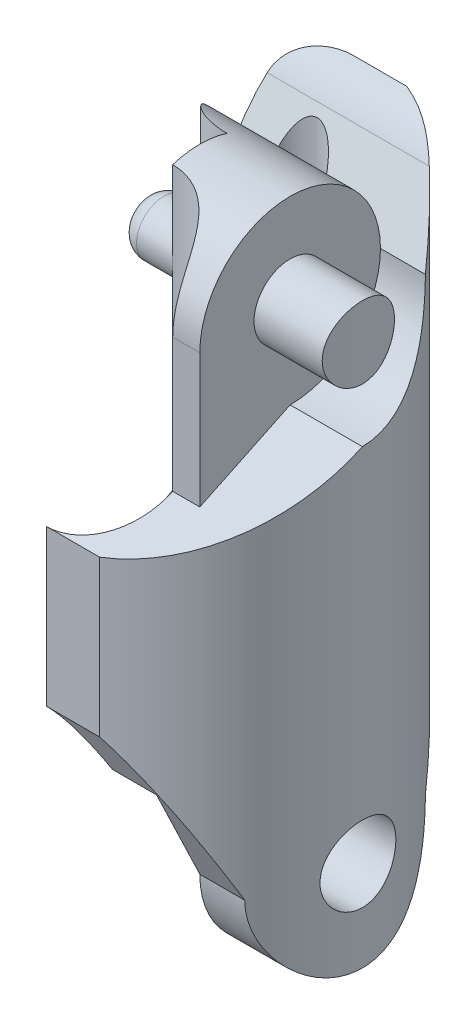
SolidWorks part; units mm, degrees
ref_plane "Front Plane" through (0, 0, 0) normal (0, 0, 1) x (1, 0, 0)
ref_plane "Top Plane" through (0, 0, 0) normal (0, 1, 0) x (1, 0, 0)
ref_plane "Right Plane" through (0, 0, 0) normal (1, 0, 0) x (0, 0, -1)
sketch "Sketch1" plane through (0, 0, 0) normal (0, 1, 0) x (1, 0, 0)
  line L0 (-2.958, 8.5) -> (2.958, 8.5)
  line L1 (-2.958, -8.5) -> (2.958, -8.5)
  arc A0 (-2.958, 8.5) -> (-2.958, -8.5) centre (0, 0) ccw
  arc A1 (2.958, 8.5) -> (2.958, -8.5) centre (0, 0) cw
  point P9 (-9, 0)
  point P10 (9, 0)
  dimension "D1" = 18
  dimension "D2" = 17
extrude "Boss-Extrude1" add sketch "Sketch1" along normal blind 35
sketch "Sketch2" plane through (0, 0, 0) normal (0, -1, 0) x (1, 0, 0)
  line L0 (1.5, -5) -> (-1.5, -5)
  line L1 (1.5, 5) -> (-1.5, 5)
  line L2 (0, 5) -> (0, -5) construction
  arc A0 (-1.5, -5) -> (1.5, -5) centre (0, -5) ccw
  arc A1 (1.5, 5) -> (-1.5, 5) centre (0, 5) ccw
  dimension "D1" = 10
  dimension "D2" = 1.5
extrude "Cut-Extrude1" cut sketch "Sketch2" against normal blind 35
sketch "Sketch3" plane through (0, 0, -8.5) normal (0, 0, -1) x (-1, 0, 0)
  line L0 (5, 0) -> (5, 10)
  line L1 (5, 10) -> (-5, 10)
  line L2 (-5, 10) -> (-5, 0)
  line L3 (5, 0) -> (-5, 0)
  line L4 (-2.958, 0) -> (2.958, 0) construction
  point P10 (0, 0)
  dimension "D1" = 10
  dimension "D2" = 10
extrude "Cut-Extrude2" cut sketch "Sketch3" against normal up to surface (17 mm away) up to face at (0, 17.5, 8.5)
sketch "Sketch4" plane through (5, 0, 0) normal (-1, 0, 0) x (0, 0, 1)
  line L0 (-7.4833, 10) -> (-5, 5)
  line L1 (8.5, 12.3086) -> (5, 5)
  line L2 (7.4833, 0) -> (-7.4833, 0) construction
  line L3 (-7.4833, 10) -> (-9.8579, -1.8222)
  line L4 (-9.8579, -1.8222) -> (9.8579, -1.8222)
  line L6 (8.5, 35) -> (8.5, 10) construction
  line L7 (9.8579, -1.8222) -> (8.5, 12.3086)
  arc A0 (-5, 5) -> (5, 5) centre (0, 5) ccw
  circle A1 centre (0, 5) radius 2.1
  point P7 (0, 0)
  dimension "D1" = 4.2
  dimension "D2" = 5
  dimension "D3" = 12.0584
  dimension "D4" = 37.769
extrude "Cut-Extrude3" cut sketch "Sketch4" against normal mid plane 35
ref_plane "Plane1" through (-2.958, 0, 0) normal (-1, 0, 0) x (0, 0, 1)
sketch "Sketch6" plane through (-2.958, 0, 0) normal (-1, 0, 0) x (0, 0, 1)
  line L0 (8.5, 20.9294) -> (0, 25)
  line L1 (8.5, 35) -> (8.5, 12.3086) construction
  line L2 (-5, 30) -> (-6.7559, 33.5353)
  line L3 (8.5, 35) -> (-8.5, 35) construction
  line L4 (8.5, 20.9294) -> (17.803, 42.886)
  line L6 (-7.4833, 10) -> (-5, 5) construction
  line L7 (-8.5, 35) -> (17.803, 42.886)
  line L8 (5, 5) -> (8.5, 12.3086) construction
  arc A0 (0, 25) -> (-5, 30) centre (0, 30) cw
  circle A1 centre (0, 30) radius 2
  arc A2 (-6.7559, 33.5353) -> (-8.5, 35) centre (-9.3069, 32.2683) ccw
  dimension "D1" = 5
  dimension "D3" = 4
  dimension "D2" = 5
  dimension "D4" = 8.5
  dimension "D5" = 90
extrude "Cut-Extrude5" cut sketch "Sketch6" against normal blind 9.6 from surface starting at face at (5, 7.1, 0)
sketch "Sketch7" plane through (5, 0, 0) normal (1, 0, 0) x (0, 0, -1)
  line L0 (5, 30) -> (6.7559, 33.5353)
  line L2 (-8.3419, 47.5367) -> (-13.1682, 33.5285)
  line L3 (-7.4833, 35) -> (7.4833, 35) construction
  line L4 (-5, 30) -> (-5, 22.6055)
  line L5 (-7.4833, 21.4163) -> (0, 25) construction
  line L6 (-5, 22.6055) -> (-9.913, 20.2527)
  line L7 (-9.913, 20.2527) -> (-13.1682, 33.5285)
  line L8 (6.7559, 33.5353) -> (5, 30) construction
  line L9 (8.5, 35) -> (-8.3419, 47.5367)
  arc A0 (5, 30) -> (-5, 30) centre (0, 30) ccw
  arc A1 (6.7559, 33.5353) -> (8.5, 35) centre (9.3069, 32.2683) cw
  arc A2 (7.4833, 34.4564) -> (6.7559, 33.5353) centre (9.3069, 32.2683) ccw construction
  dimension "D1" = 5
fillet "Fillet3" radius 1 4 edges at (0, 10, 6.5) (0, 10, 5) (0, 10, -6.5) (0, 10, -5)
extrude "Cut-Extrude6" cut sketch "Sketch6<3>" along normal blind 6.604 from surface starting at face at (-5, 2.9, 0)
sketch "Sketch6<3>" plane through (-2.958, 0, 0) normal (-1, 0, 0) x (0, 0, 1) same geometry as "Sketch6"
extrude "Cut-Extrude7" cut sketch "Sketch7" against normal blind 14.986
sketch "Sketch8" plane through (0, 10, 0) normal (0, -1, 0) x (1, 0, 0)
  line L0 (0, 1.5) -> (0, -1.5)
  line L1 (-2.958, -8.5) -> (2.958, -8.5) construction
  line L2 (2.958, 8.5) -> (-2.958, 8.5) construction
  line L3 (0, 8.5) -> (-4.7901, 15.219)
  line L4 (-4.7901, 15.219) -> (-17.8556, -9.7177)
  line L5 (-17.8556, -9.7177) -> (-4.7901, -16.0136)
  line L6 (-4.7901, -16.0136) -> (0, -8.5)
  arc A0 (0, -1.5) -> (0, -8.5) centre (0, -5) ccw
  arc A1 (0, 1.5) -> (0, 8.5) centre (0, 5) ccw
  arc A4 (2.2913, 4) -> (0.7187, 7.3945) centre (0, 5) ccw construction
  arc A5 (-2.2913, -4) -> (2.2913, -4) centre (0, -5) ccw construction
extrude "Cut-Extrude8" cut sketch "Sketch8" against normal mid plane 62.992
sketch "Sketch9" plane through (0, 0, 0) normal (-1, 0, 0) x (0, 0, 1)
  line L0 (7.3945, 10) -> (-7.4833, 10) construction
  circle A0 centre (0, 16) radius 1.5
  dimension "D2" = 3
  dimension "D1" = 6
extrude "Cut-Extrude9" cut sketch "Sketch9" against normal blind 8.382
sketch "Sketch11" plane through (0, 0, 0) normal (-1, 0, 0) x (0, 0, 1)
  circle A0 centre (0, 16) radius 2
  dimension "D1" = 4
extrude "Cut-Extrude10" cut sketch "Sketch11" against normal mid plane 6.2
sketch "Sketch12" plane through (0, 0, 0) normal (-1, 0, 0) x (0, 0, 1)
  line L0 (0, 18) -> (0, 19.5)
  line L1 (0, 14) -> (0, 12.5)
  arc A0 (1.5, 17.3229) -> (-1.5, 17.3229) centre (0, 16) ccw construction
  arc A1 (-1.5, 14.6771) -> (1.5, 14.6771) centre (0, 16) ccw construction
  arc A2 (0, 19.5) -> (0, 12.5) centre (0, 16) cw
  arc A3 (1.5, 14.6771) -> (1.5, 17.3229) centre (0, 16) ccw construction
  arc A4 (0, 18) -> (0, 14) centre (0, 16) cw
  dimension "D1" = 1.5
extrude "Boss-Extrude2" add sketch "Sketch12" against normal blind 3.862
sketch "Sketch13" plane through (0, 0, 0) normal (-1, 0, 0) x (0, 0, 1)
  line L0 (1.5, 34.7697) -> (1.5, 19.1623) construction
  circle A0 centre (0, 30) radius 1.5
  circle A1 centre (0, 30) radius 2 construction
extrude "Boss-Extrude4" add sketch "Sketch13" along normal blind 3
fillet "Fillet5" radius 1 1 edges at (-3, 30, 1.5)
